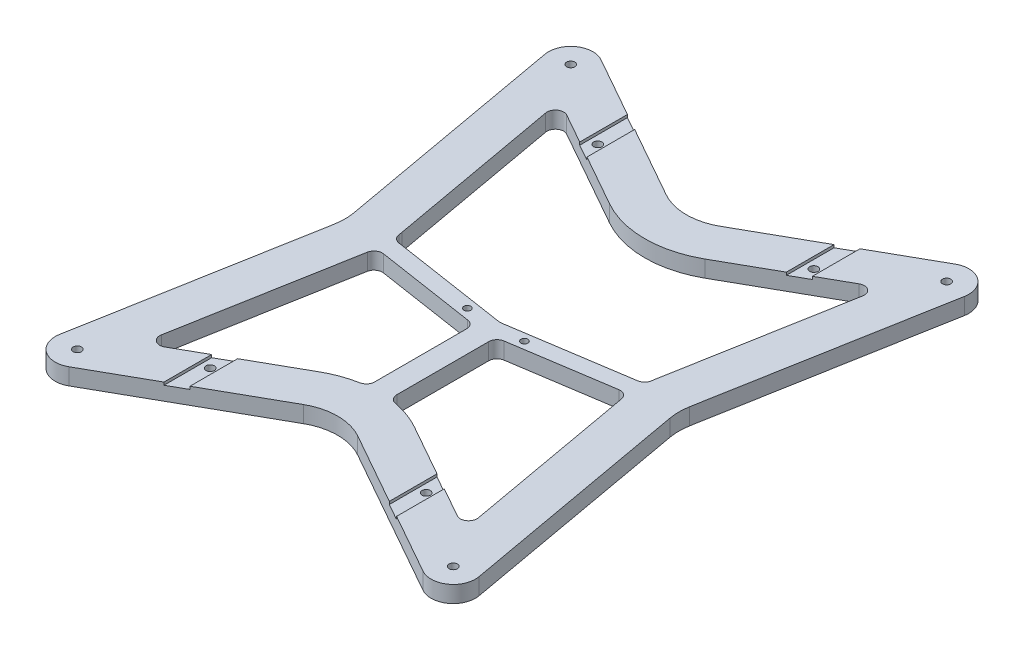
SolidWorks part; units mm, degrees
material "1060 Alloy"
ref_plane "Front Plane" through (0, 0, 0) normal (0, 0, 1) x (1, 0, 0)
ref_plane "Top Plane" through (0, 0, 0) normal (0, 1, 0) x (1, 0, 0)
ref_plane "Right Plane" through (0, 0, 0) normal (1, 0, 0) x (0, 0, -1)
sketch "Sketch1" plane through (0, 0, 0) normal (0, 1, 0) x (1, 0, 0)
  line L0 (-63.9527, 96.0638) -> (0, 60)
  line L1 (0, 60) -> (63.9527, 96.0638)
  line L2 (75.7561, 87.6805) -> (60, 0)
  line L3 (60, 0) -> (75.7561, -87.6805)
  line L4 (63.9527, -96.0638) -> (0, -60)
  line L5 (0, -60) -> (-63.9527, -96.0638)
  line L6 (-75.7561, -87.6805) -> (-60, 0)
  line L7 (-60, 0) -> (-75.7561, 87.6805)
  line L8 (-78.4889, 78.4889) -> (78.4889, -78.4889) construction
  line L9 (-42, 80) -> (-36, 80) construction
  line L10 (-42, 80) -> (-42, 60) construction
  line L11 (-42, 60) -> (-36, 60) construction
  line L12 (-36, 80) -> (-36, 60) construction
  line L13 (-42, 80) -> (-36, 60) construction
  line L14 (-42, 60) -> (-36, 80) construction
  line L15 (36, 80) -> (42, 80) construction
  line L16 (36, 80) -> (36, 60) construction
  line L17 (36, 60) -> (42, 60) construction
  line L18 (42, 80) -> (42, 60) construction
  line L19 (36, 80) -> (42, 60) construction
  line L20 (36, 60) -> (42, 80) construction
  line L21 (36, -60) -> (42, -60) construction
  line L22 (36, -60) -> (36, -80) construction
  line L23 (36, -80) -> (42, -80) construction
  line L24 (42, -60) -> (42, -80) construction
  line L25 (36, -60) -> (42, -80) construction
  line L26 (36, -80) -> (42, -60) construction
  line L27 (-42, -60) -> (-36, -60) construction
  line L28 (-42, -60) -> (-42, -80) construction
  line L29 (-42, -80) -> (-36, -80) construction
  line L30 (-36, -60) -> (-36, -80) construction
  line L31 (-42, -60) -> (-36, -80) construction
  line L32 (-42, -80) -> (-36, -60) construction
  line L33 (111, 45.9777) -> (45.9777, 111) construction
  line L34 (45.9777, 111) -> (-45.9777, 111) construction
  line L35 (-45.9777, 111) -> (-111, 45.9777) construction
  line L36 (-111, 45.9777) -> (-111, -45.9777) construction
  line L37 (-111, -45.9777) -> (-45.9777, -111) construction
  line L38 (-45.9777, -111) -> (45.9777, -111) construction
  line L39 (45.9777, -111) -> (111, -45.9777) construction
  line L40 (111, -45.9777) -> (111, 45.9777) construction
  line L41 (78.4889, 78.4889) -> (-78.4889, -78.4889) construction
  circle A0 centre (-67.8823, 89.0955) radius 1.5
  circle A1 centre (67.8823, 89.0955) radius 1.5
  circle A2 centre (-67.8823, -89.0955) radius 1.5
  circle A3 centre (67.8823, -89.0955) radius 1.5
  arc A4 (-63.9527, 96.0638) -> (-75.7561, 87.6805) centre (-67.8823, 89.0955) ccw
  arc A5 (63.9527, 96.0638) -> (75.7561, 87.6805) centre (67.8823, 89.0955) cw
  arc A6 (-75.7561, -87.6805) -> (-63.9527, -96.0638) centre (-67.8823, -89.0955) ccw
  arc A7 (75.7561, -87.6805) -> (63.9527, -96.0638) centre (67.8823, -89.0955) cw
  circle A8 centre (0, 0) radius 111 construction
  circle A9 centre (-39, 70) radius 1.5
  circle A10 centre (39, 70) radius 1.5
  circle A11 centre (39, -70) radius 1.5
  circle A12 centre (-39, -70) radius 1.5
  ellipse E0 centre (0, 0) end of major axis (0, -60) minor radius 60 construction
  dimension "D5" = 3
  dimension "D6" = 60
  dimension "D7" = 8
  dimension "D12" = 3
  dimension "D3" = 15
  dimension "D4" = 15
  dimension "D8" = 140
  dimension "D9" = 78
  dimension "D10" = 0
  dimension "D11" = 70
  dimension "D13" = 60
  dimension "D14" = 39
  dimension "D15" = 20
  dimension "D16" = 6
  dimension "D17" = 111
  dimension "D18" = 15
extrude "Boss-Extrude1" add sketch "Sketch1" along normal blind 6
fillet "Fillet1" radius 20 4 edges at (0, 3, -60) (-60, 3, 0) (0, 3, 60) (60, 3, 0)
sketch "Sketch2" plane through (0, 6, 0) normal (0, 1, 0) x (1, 0, 0)
  line L44 (-58.3612, 75.6901) -> (-45.8721, 6.1903)
  line L45 (-45.8721, -6.1903) -> (-58.3612, -75.6901)
  line L46 (-58.3612, -75.6901) -> (-17.1919, -52.4741)
  line L47 (17.1919, -52.4741) -> (58.3612, -75.6901)
  line L48 (58.3612, -75.6901) -> (45.8721, -6.1903)
  line L49 (45.8721, 6.1903) -> (58.3612, 75.6901)
  line L50 (58.3612, 75.6901) -> (17.1919, 52.4741)
  line L51 (-17.1919, 52.4741) -> (-58.3612, 75.6901)
  line L52 (-58.3612, 75.6901) -> (-45.8721, 6.1903)
  line L53 (-45.8721, -6.1903) -> (-58.3612, -75.6901)
  line L54 (-58.3612, -75.6901) -> (-17.1919, -52.4741)
  line L55 (17.1919, -52.4741) -> (58.3612, -75.6901)
  line L56 (58.3612, -75.6901) -> (45.8721, -6.1903)
  line L57 (45.8721, 6.1903) -> (58.3612, 75.6901)
  line L58 (58.3612, 75.6901) -> (17.1919, 52.4741)
  line L59 (-17.1919, 52.4741) -> (-58.3612, 75.6901)
  arc A40 (-45.8721, -6.1903) -> (-45.8721, 6.1903) centre (-80.3204, 0) ccw
  arc A41 (17.1919, -52.4741) -> (-17.1919, -52.4741) centre (0, -82.9608) ccw
  arc A42 (45.8721, 6.1903) -> (45.8721, -6.1903) centre (80.3204, 0) ccw
  arc A43 (-17.1919, 52.4741) -> (17.1919, 52.4741) centre (0, 82.9608) ccw
  arc A44 (-45.8721, -6.1903) -> (-45.8721, 6.1903) centre (-80.3204, 0) ccw
  arc A45 (17.1919, -52.4741) -> (-17.1919, -52.4741) centre (0, -82.9608) ccw
  arc A46 (45.8721, 6.1903) -> (45.8721, -6.1903) centre (80.3204, 0) ccw
  arc A47 (-17.1919, 52.4741) -> (17.1919, 52.4741) centre (0, 82.9608) ccw
  dimension "D1" = 15
extrude "Cut-Extrude1" cut sketch "Sketch2" against normal up to next
sketch "Sketch5" plane through (0, 6, 0) normal (0, 1, 0) x (1, 0, 0)
  line L0 (-47.8657, 2.9653) -> (0, -4.3743)
  line L1 (-12.94, -8.43) -> (12.94, -8.43) construction
  line L2 (-12.94, -8.43) -> (-12.94, 8.43) construction
  line L3 (-12.94, 8.43) -> (12.94, 8.43) construction
  line L4 (12.94, -8.43) -> (12.94, 8.43) construction
  line L5 (-12.94, -8.43) -> (12.94, 8.43) construction
  line L6 (-12.94, 8.43) -> (12.94, -8.43) construction
  line L8 (0, -4.3743) -> (47.8657, 2.9653)
  line L10 (47.8657, 2.9653) -> (48.7751, -2.9653)
  line L11 (48.7751, -2.9653) -> (4, -9.8311)
  line L12 (4, -9.8311) -> (4, -48.1902)
  line L13 (-4, -48.1902) -> (-4, -9.8311)
  line L14 (-4, -9.8311) -> (-48.7751, -2.9653)
  line L15 (-48.7751, -2.9653) -> (-47.8657, 2.9653)
  line L17 (48.3204, 0) -> (-48.3204, 0) construction
  circle A0 centre (-10.3, -5.83) radius 1.25
  circle A1 centre (10.3, -5.83) radius 1.25
  arc A2 (17.1919, -52.4741) -> (-17.1919, -52.4741) centre (0, -82.9608) ccw construction
  arc A3 (4, -48.1902) -> (-4, -48.1902) centre (0, -82.9608) ccw
  arc A4 (-45.8721, -6.1903) -> (-45.8721, 6.1903) centre (-80.3204, 0) ccw construction
  arc A5 (45.8721, 6.1903) -> (45.8721, -6.1903) centre (80.3204, 0) ccw construction
  circle A6 centre (48.3204, 0) radius 3 construction
  circle A7 centre (-48.3204, 0) radius 3 construction
  point P0 (0, 0)
  dimension "D3" = 2.5
  dimension "D10" = 6
  dimension "D1" = 16.86
  dimension "D2" = 25.88
  dimension "D4" = 20.6
  dimension "D5" = 2.64
  dimension "D6" = 2.6
  dimension "D7" = 6
  dimension "D8" = 3
  dimension "D9" = 8
extrude "Boss-Extrude2" add sketch "Sketch5" against normal up to surface (6 mm away) up to face at (0, 0, 0)
fillet "Fillet2" radius 3 13 edges at (58.3612, 3, 75.6901) (-58.3612, 3, 75.6901) (58.3612, 3, -75.6901) (-58.3612, 3, -75.6901) (0, 3, 4.3743) (4, 3, 9.8311) (4, 3, 48.1902) (-4, 3, 48.1902) (-4, 3, 9.8311) (45.4163, 3, -2.5898) (-45.4163, 3, -2.5898) (45.4927, 3, 3.4687) (-45.4927, 3, 3.4687)
sketch "Sketch6" plane through (0, 6, 0) normal (0, 1, 0) x (1, 0, 0)
  line L0 (-9.8239, 65.5399) -> (-63.9527, 96.0638) construction
  line L1 (-42, -58) -> (-36, -58)
  line L2 (-42, -58) -> (-42, -83.6844)
  line L3 (-42, -83.6844) -> (-36, -83.6844)
  line L4 (-36, -58) -> (-36, -83.6844)
  line L5 (36, -58) -> (42, -58)
  line L6 (36, -58) -> (36, -83.6844)
  line L7 (36, -83.6844) -> (42, -83.6844)
  line L8 (42, -58) -> (42, -83.6844)
  line L9 (36, 58) -> (42, 58)
  line L10 (36, 58) -> (36, 83.6844)
  line L11 (36, 83.6844) -> (42, 83.6844)
  line L12 (42, 58) -> (42, 83.6844)
  line L13 (-42, 58) -> (-36, 58)
  line L14 (-42, 58) -> (-42, 83.6844)
  line L15 (-42, 83.6844) -> (-36, 83.6844)
  line L16 (-36, 58) -> (-36, 83.6844)
  line L17 (63.9527, 96.0638) -> (9.8239, 65.5399) construction
  line L18 (9.8239, -65.5399) -> (63.9527, -96.0638) construction
  line L19 (-63.9527, -96.0638) -> (-9.8239, -65.5399) construction
  circle A0 centre (-39, -70) radius 1.5 construction
  circle A1 centre (39, -70) radius 1.5 construction
  circle A2 centre (-39, 70) radius 1.5 construction
  dimension "D2" = 3
  dimension "D3" = 3
  dimension "D5" = 12
  dimension "D1" = 6
  dimension "D4" = 12
extrude "Cut-Extrude2" cut sketch "Sketch6" against normal blind 1
equation "\"D14@Sketch1\"=\"D9@Sketch1\"/2"
